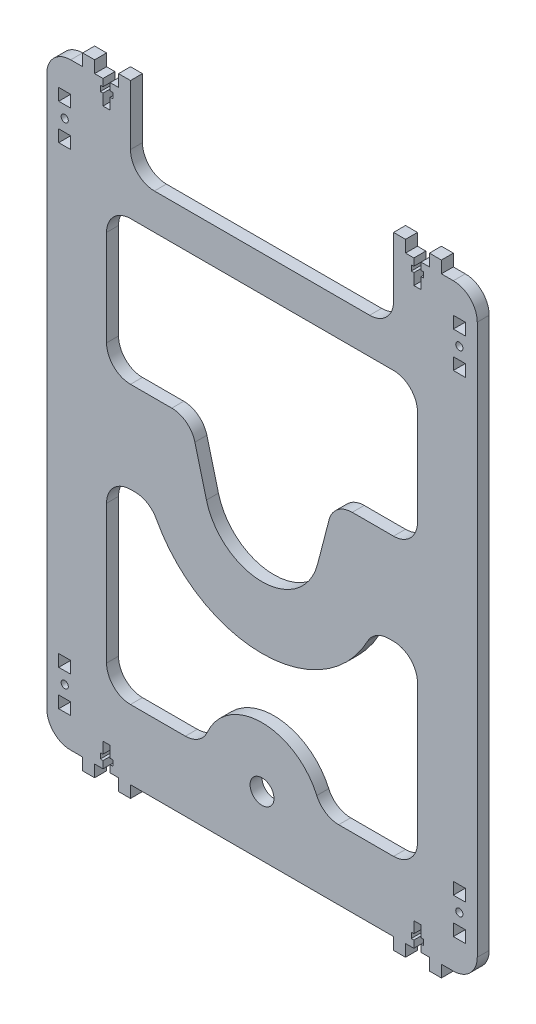
SolidWorks part; units mm, degrees
ref_plane "Front Plane" through (0, 0, 0) normal (0, 0, 1) x (1, 0, 0)
ref_plane "Top Plane" through (0, 0, 0) normal (0, 1, 0) x (1, 0, 0)
ref_plane "Right Plane" through (0, 0, 0) normal (1, 0, 0) x (0, 0, -1)
sketch "Sketch1" plane through (0, 0, 0) normal (0, 0, 1) x (1, 0, 0)
  line L0 (0, 0) -> (187.0096, 0) construction
  line L1 (-90, 125) -> (-55, 125) construction
  line L2 (-90, 125) -> (-90, -125)
  line L3 (-90, -125) -> (90, -125)
  line L4 (90, 125) -> (90, -125)
  line L5 (0, 0) -> (0, 134.5508) construction
  line L6 (-23.2273, -6.0409) -> (-30, 20)
  line L7 (-65, 80) -> (65, 80)
  line L8 (65, 80) -> (65, 0) construction
  line L9 (65, 0) -> (-65, 0) construction
  line L10 (-65, 0) -> (-65, 80) construction
  line L11 (-65, 0) -> (-20, 0) construction
  line L12 (20, 0) -> (65, 0) construction
  line L13 (82.5, 125) -> (82.5, -125) construction
  line L14 (0, 0) -> (0, -125) construction
  line L21 (-30, 20) -> (-65, 20)
  line L22 (-65, 20) -> (-65, 80)
  line L23 (65, 20) -> (65, 80)
  line L24 (30, 20) -> (65, 20)
  line L26 (-90, 125) -> (-55, 125)
  line L27 (23.2273, -6.0409) -> (30, 20)
  line L28 (-55, 125) -> (-55, 95)
  line L29 (-55, 95) -> (55, 95)
  line L30 (55, 95) -> (55, 125)
  line L31 (55, 125) -> (90, 125) construction
  line L32 (55, 125) -> (90, 125)
  line L33 (-46.616, -18.0816) -> (-65, -18.0816)
  line L34 (-65, -18.0816) -> (-65, -95.958)
  line L35 (-65, -95.958) -> (-24.6711, -95.958)
  line L36 (46.616, -18.0816) -> (65, -18.0816)
  line L37 (65, -18.0816) -> (65, -95.958)
  line L38 (65, -95.958) -> (24.6711, -95.958)
  circle A1 centre (0, -100) radius 5
  circle A2 centre (0, 0) radius 24 construction
  arc A3 (23.2273, -6.0409) -> (-23.2273, -6.0409) centre (0, 0) cw
  circle A4 centre (0, 0) radius 50 construction
  circle A5 centre (0, -100) radius 25 construction
  arc A6 (24.6711, -95.958) -> (-24.6711, -95.958) centre (0, -100) ccw
  arc A7 (-46.616, -18.0816) -> (46.616, -18.0816) centre (0, 0) ccw
  line B0 (82.5, 107.5) -> (82.5, 97.5) construction
  line B1 (80, 107.5) -> (80, 112.5)
  line B2 (80, 107.5) -> (85, 107.5)
  line B3 (85, 107.5) -> (85, 112.5)
  line B4 (80, 112.5) -> (85, 112.5)
  line B5 (80, 97.5) -> (80, 92.5)
  line B6 (80, 97.5) -> (85, 97.5)
  line B7 (85, 97.5) -> (85, 92.5)
  line B8 (80, 92.5) -> (85, 92.5)
  line B9 (82.5, 102.5) -> (75.5276, 102.5) construction
  circle B10 centre (82.5, 102.5) radius 1.5
  line B11 (82.5, -107.5) -> (82.5, -97.5) construction
  line B12 (80, -107.5) -> (80, -112.5)
  line B13 (80, -107.5) -> (85, -107.5)
  line B14 (85, -107.5) -> (85, -112.5)
  line B15 (80, -112.5) -> (85, -112.5)
  line B16 (80, -97.5) -> (80, -92.5)
  line B17 (80, -97.5) -> (85, -97.5)
  line B18 (85, -97.5) -> (85, -92.5)
  line B19 (80, -92.5) -> (85, -92.5)
  line B20 (82.5, -102.5) -> (75.5276, -102.5) construction
  circle B21 centre (82.5, -102.5) radius 1.5
  line B22 (-82.5, 107.5) -> (-82.5, 97.5) construction
  line B23 (-80, 107.5) -> (-80, 112.5)
  line B24 (-80, 107.5) -> (-85, 107.5)
  line B25 (-85, 107.5) -> (-85, 112.5)
  line B26 (-80, 112.5) -> (-85, 112.5)
  line B27 (-80, 97.5) -> (-80, 92.5)
  line B28 (-80, 97.5) -> (-85, 97.5)
  line B29 (-85, 97.5) -> (-85, 92.5)
  line B30 (-80, 92.5) -> (-85, 92.5)
  line B31 (-82.5, 102.5) -> (-75.5276, 102.5) construction
  circle B32 centre (-82.5, 102.5) radius 1.5
  line B33 (-82.5, -107.5) -> (-82.5, -97.5) construction
  line B34 (-80, -107.5) -> (-80, -112.5)
  line B35 (-80, -107.5) -> (-85, -107.5)
  line B36 (-85, -107.5) -> (-85, -112.5)
  line B37 (-80, -112.5) -> (-85, -112.5)
  line B38 (-80, -97.5) -> (-80, -92.5)
  line B39 (-80, -97.5) -> (-85, -97.5)
  line B40 (-85, -97.5) -> (-85, -92.5)
  line B41 (-80, -92.5) -> (-85, -92.5)
  line B42 (-82.5, -102.5) -> (-75.5276, -102.5) construction
  circle B43 centre (-82.5, -102.5) radius 1.5
  line B44 (-67.6, -122) -> (-67.6, -119.7)
  line B45 (-63.5, -119.7) -> (-63.5, -115)
  line B46 (-66.5, -115) -> (-66.5, -119.7)
  line B47 (-67.6, -119.7) -> (-66.5, -119.7)
  line B48 (-65, -125) -> (-65, -113.7792) construction
  line B49 (-66.5, -125) -> (-70, -125)
  line B50 (-70, -130) -> (-75, -130)
  line B51 (-75, -130) -> (-75, -125)
  line B52 (-70, -130) -> (-70, -125)
  line B53 (-63.5, -125) -> (-60, -125)
  line B54 (-60, -125) -> (-60, -130)
  line B55 (-60, -130) -> (-55, -130)
  line B56 (-55, -130) -> (-55, -125)
  line B57 (-66.5, -125) -> (-63.5, -125) construction
  line B58 (-63.5, -125) -> (-63.5, -122)
  line B59 (-63.5, -119.7) -> (-62.4, -119.7)
  line B60 (-62.4, -122) -> (-63.5, -122)
  line B61 (-63.5, -115) -> (-66.5, -115)
  line B62 (-66.5, -122) -> (-67.6, -122)
  line B63 (-62.4, -119.7) -> (-62.4, -122)
  line B64 (-66.5, -122) -> (-66.5, -125)
  line B65 (-65, -115) -> (-65, -125) construction
  line B66 (62.4, -122) -> (62.4, -119.7)
  line B67 (66.5, -119.7) -> (66.5, -115)
  line B68 (63.5, -115) -> (63.5, -119.7)
  line B69 (62.4, -119.7) -> (63.5, -119.7)
  line B70 (65, -125) -> (65, -113.7792) construction
  line B71 (63.5, -125) -> (60, -125)
  line B72 (60, -130) -> (55, -130)
  line B73 (55, -130) -> (55, -125)
  line B74 (60, -130) -> (60, -125)
  line B75 (66.5, -125) -> (70, -125)
  line B76 (70, -125) -> (70, -130)
  line B77 (70, -130) -> (75, -130)
  line B78 (75, -130) -> (75, -125)
  line B79 (63.5, -125) -> (66.5, -125) construction
  line B80 (66.5, -125) -> (66.5, -122)
  line B81 (66.5, -119.7) -> (67.6, -119.7)
  line B82 (67.6, -122) -> (66.5, -122)
  line B83 (66.5, -115) -> (63.5, -115)
  line B84 (63.5, -122) -> (62.4, -122)
  line B85 (67.6, -119.7) -> (67.6, -122)
  line B86 (63.5, -122) -> (63.5, -125)
  line B87 (65, -115) -> (65, -125) construction
  line B88 (67.6, 122) -> (67.6, 119.7)
  line B89 (63.5, 119.7) -> (63.5, 115)
  line B90 (66.5, 115) -> (66.5, 119.7)
  line B91 (67.6, 119.7) -> (66.5, 119.7)
  line B92 (65, 125) -> (65, 113.7792) construction
  line B93 (66.5, 125) -> (70, 125)
  line B94 (70, 130) -> (75, 130)
  line B95 (75, 130) -> (75, 125)
  line B96 (70, 130) -> (70, 125)
  line B97 (63.5, 125) -> (60, 125)
  line B98 (60, 125) -> (60, 130)
  line B99 (60, 130) -> (55, 130)
  line B100 (55, 130) -> (55, 125)
  line B101 (66.5, 125) -> (63.5, 125) construction
  line B102 (63.5, 125) -> (63.5, 122)
  line B103 (63.5, 119.7) -> (62.4, 119.7)
  line B104 (62.4, 122) -> (63.5, 122)
  line B105 (63.5, 115) -> (66.5, 115)
  line B106 (66.5, 122) -> (67.6, 122)
  line B107 (62.4, 119.7) -> (62.4, 122)
  line B108 (66.5, 122) -> (66.5, 125)
  line B109 (65, 115) -> (65, 125) construction
  line B110 (-62.4, 122) -> (-62.4, 119.7)
  line B111 (-66.5, 119.7) -> (-66.5, 115)
  line B112 (-63.5, 115) -> (-63.5, 119.7)
  line B113 (-62.4, 119.7) -> (-63.5, 119.7)
  line B114 (-65, 125) -> (-65, 113.7792) construction
  line B115 (-63.5, 125) -> (-60, 125)
  line B116 (-60, 130) -> (-55, 130)
  line B117 (-55, 130) -> (-55, 125)
  line B118 (-60, 130) -> (-60, 125)
  line B119 (-66.5, 125) -> (-70, 125)
  line B120 (-70, 125) -> (-70, 130)
  line B121 (-70, 130) -> (-75, 130)
  line B122 (-75, 130) -> (-75, 125)
  line B123 (-63.5, 125) -> (-66.5, 125) construction
  line B124 (-66.5, 125) -> (-66.5, 122)
  line B125 (-66.5, 119.7) -> (-67.6, 119.7)
  line B126 (-67.6, 122) -> (-66.5, 122)
  line B127 (-66.5, 115) -> (-63.5, 115)
  line B128 (-63.5, 122) -> (-62.4, 122)
  line B129 (-67.6, 119.7) -> (-67.6, 122)
  line B130 (-63.5, 122) -> (-63.5, 125)
  line B131 (-65, 115) -> (-65, 125) construction
  dimension "D8" = 50
  dimension "D10" = 10
  dimension "D2" = 24
  dimension "D13" = 100
  dimension "D3" = 250
  dimension "D4" = 180
  dimension "D5" = 35
  dimension "D6" = 25
  dimension "D7" = 20
  dimension "D9" = 22.5
  dimension "D11" = 25
  dimension "D12" = 7.5
  dimension "D14" = 15
  dimension "D15" = 30
sketch_block_instance "Trou M3 plots 5mm-7"
sketch_block "Trou M3 plots 5mm" parameters "D2"=3, "D1"=5, "D3"=5, "D4"=10
sketch_block_instance "Trou M3 plots 5mm-8"
sketch_block_instance "Trou M3 plots 5mm-9"
sketch_block_instance "Trou M3 plots 5mm-10"
sketch_block_instance "Insert M3 plots ep 5mm-1"
sketch_block "Insert M3 plots ep 5mm" parameters "D1"=10, "D2"=5, "D3"=5
sketch_block_instance "Decoupe Insert M3-4"
sketch_block "Decoupe Insert M3" parameters "D1"=5.2, "D2"=3, "D3"=2.3, "D4"=3, "D5"=10
sketch_block_instance "Insert M3 plots ep 5mm-2"
sketch_block_instance "Insert M3 plots ep 5mm-3"
sketch_block_instance "Insert M3 plots ep 5mm-5"
extrude "Boss-Extrude1" add sketch "Sketch1" along normal blind 5 contours B130 B128 B110 B113 B112 B127 B111 B125 B129 B126 B124 L26 L2 L3 B64 B62 B44 B47 B46 B61 B45 B59 B63 B60 B58 B86 B84 B66 B69 B68 B83 B67 B81 B85 B82 B80 L4 | B50 B52 L3 B51 | B55 B56 L3 B54 | B72 B74 L3 B73 | B77 B78 L3 B76 | B121 B122 L26 B120 | B116 B118 L26 B117 | B99 B100 L26 B98 | B94 B96 L26 B95 region at (-82.5, 121.9194, 0) region at (-72.5, 127.5, 0) region at (-72.5, -127.5, 0) region at (-57.5, 127.5, 0) region at (-57.5, -127.5, 0) region at (57.5, -127.5, 0) region at (57.5, 127.5, 0) region at (72.5, -127.5, 0) region at (72.5, 127.5, 0)
fillet "Fillet1" radius 10 20 edges at (-90, -125, 2.5) (90, -125, 2.5) (-90, 125, 2.5) (90, 125, 2.5) (-55, 95, 2.5) (55, 95, 2.5) (24.6711, -95.958, 2.5) (-24.6711, -95.958, 2.5) (-65, -95.958, 2.5) (65, -95.958, 2.5) (65, -18.0816, 2.5) (46.616, -18.0816, 2.5) (-46.616, -18.0816, 2.5) (-65, -18.0816, 2.5) (65, 80, 2.5) (-65, 80, 2.5) (65, 20, 2.5) (-65, 20, 2.5) (30, 20, 2.5) (-30, 20, 2.5)
